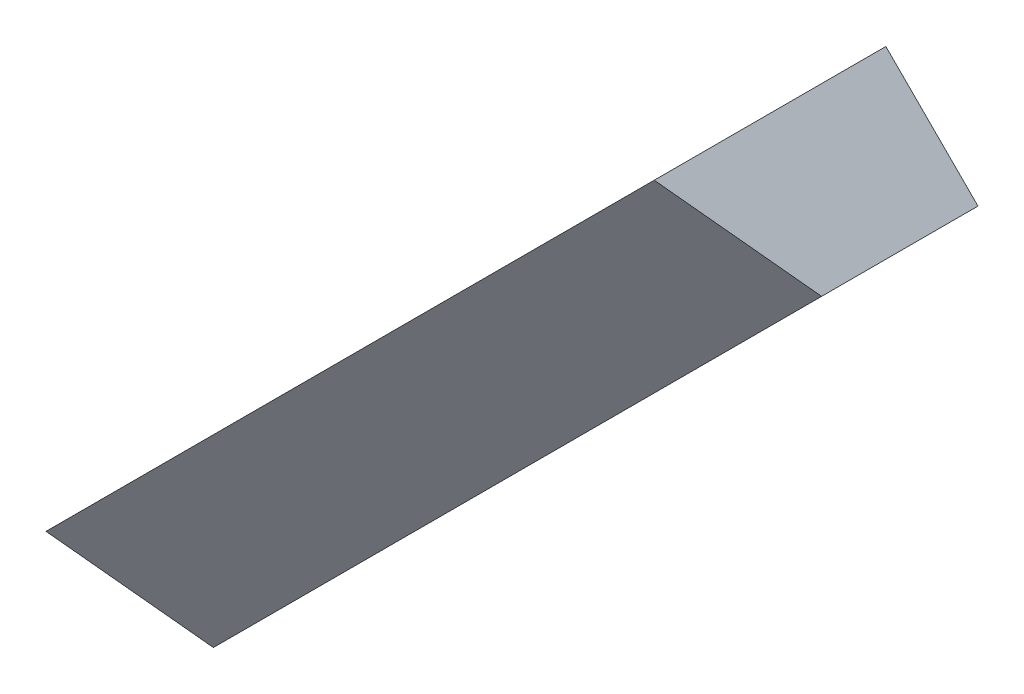
SolidWorks part; units mm, degrees
ref_plane "Alzado" through (0, 0, 0) normal (0, 0, 1) x (1, 0, 0)
ref_plane "Planta" through (0, 0, 0) normal (0, 1, 0) x (1, 0, 0)
ref_plane "Vista lateral" through (0, 0, 0) normal (1, 0, 0) x (0, 0, -1)
sketch "Croquis1" plane through (0, 0, 0) normal (0, 0, 1) x (1, 0, 0)
  line L0 (-38.7038, 2.6439) -> (-19.6119, 21.7358) construction
  line L1 (-19.6119, 21.7358) -> (-17.8442, 23.5036) construction
  line L2 (-19.6119, 21.7358) -> (-21.3797, 23.5036) construction
  line L3 (-38.7038, 2.6439) -> (-40.4716, 0.8761) construction
  line L4 (-19.2584, 25.6249) -> (-42.5929, 2.2904)
  line L5 (-19.2584, 25.6249) -> (-15.7228, 22.0893)
  line L6 (-42.5929, 2.2904) -> (-39.0574, -1.2452)
  line L7 (-39.0574, -1.2452) -> (-15.7228, 22.0893)
  line L8 (-29.1579, 12.1898) -> (-27.3901, 10.4221) construction
  circle A2 centre (-38.7038, 2.6439) radius 1.6
  circle A3 centre (-19.6119, 21.7358) radius 1.6
  dimension "D5" = 3.2
  dimension "D1" = 2.5
  dimension "D2" = 2.5
  dimension "D3" = 2.5
  dimension "D4" = 5
  dimension "D6" = 27
extrude "Saliente-Extruir1" add sketch "Croquis1" along normal blind 5
sketch "Croquis2" plane through (-20.1513, -20.1513, 0) normal (-0.7071, -0.7071, 0) x (0, 0, 1)
  line L0 (5, 26.7373) -> (6, 26.7373)
  line L1 (6, 26.7373) -> (8.8868, 31.7373)
  line L2 (8.8868, 31.7373) -> (5, 31.7373)
  line L3 (5, 31.7373) -> (5, 26.7373)
  dimension "D1" = 30
  dimension "D2" = 1
extrude "Saliente-Extruir2" add sketch "Croquis2" against normal up to surface (33 mm away) up to face at (-17.4906, 23.8571, 2.5)
sketch "Croquis3" plane through (-18.9061, 18.9061, 0) normal (0.7071, -0.7071, 0) x (0, 0, -1)
  line L0 (-6, 4.5018) -> (-6, -28.4982) construction
  line L1 (-6, -28.4982) -> (0, -28.4982) construction
  circle A0 centre (-5, -26.9982) radius 0.5
  circle A1 centre (-5, -23.9982) radius 0.5
  circle A2 centre (-5, -20.9982) radius 0.5
  circle A3 centre (-5, -17.9982) radius 0.5
  circle A4 centre (-5, -14.9982) radius 0.5
  circle A5 centre (-5, -11.9982) radius 0.5
  circle A6 centre (-5, -8.9982) radius 0.5
  circle A7 centre (-5, -5.9982) radius 0.5
  circle A8 centre (-5, -2.9982) radius 0.5
  circle A9 centre (-5, 0.0018) radius 0.5
  circle A10 centre (-5, 3.0018) radius 0.5
  dimension "D1" = 1
  dimension "D2" = 1
  dimension "D3" = 1.5
  dimension "D4" = 11
extrude "Cortar-Extruir1" cut sketch "Croquis3" along direction (0.6124, -0.6124, -0.5) on the side against the normal up to surface (5 mm away) up to face at (-30.9256, 13.9576, 4.4434)
